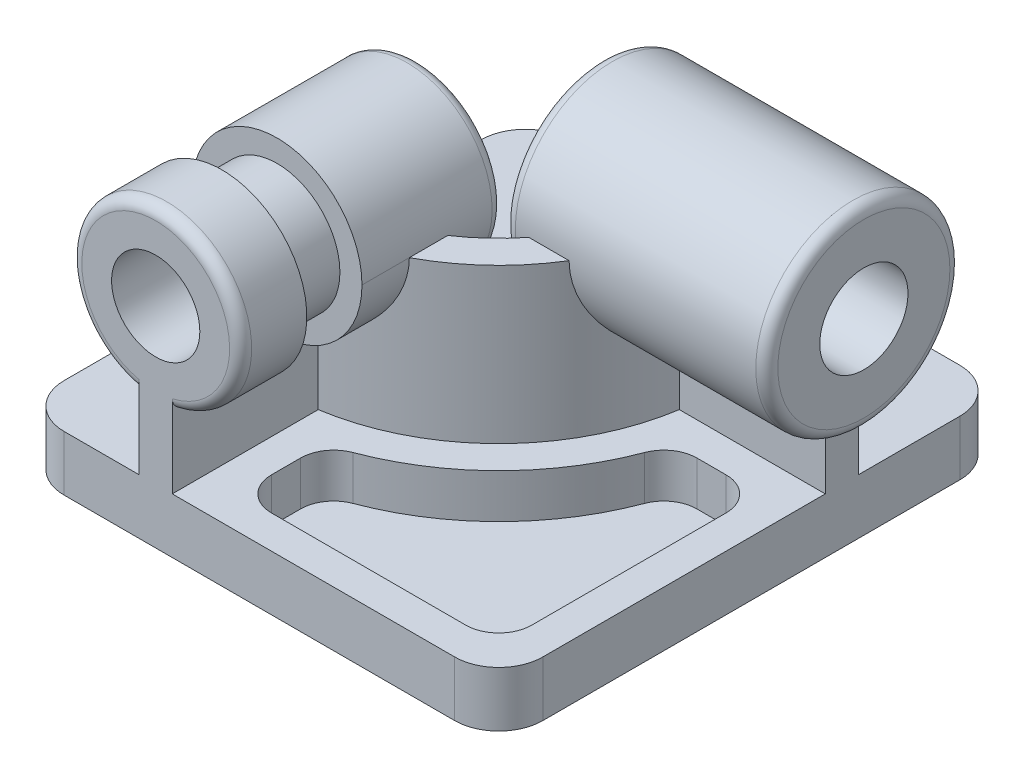
SolidWorks part; units mm, degrees
material "Alloy Steel"
ref_plane "정면" through (0, 0, 0) normal (0, 0, 1) x (1, 0, 0)
ref_plane "윗면" through (0, 0, 0) normal (0, 1, 0) x (1, 0, 0)
ref_plane "우측면" through (0, 0, 0) normal (1, 0, 0) x (0, 0, -1)
sketch "Sketch1" plane through (0, 0, 0) normal (0, 1, 0) x (1, 0, 0)
  line L0 (15, 15) -> (15, 66.1548)
  line L1 (0, 0) -> (143, 0)
  line L2 (0, 0) -> (0, 80)
  line L3 (83, 163) -> (163, 163)
  line L4 (163, 20) -> (163, 163)
  line L5 (96.8452, 148) -> (148, 148)
  line L8 (15, 15) -> (148, 15) construction
  line L9 (148, 15) -> (148, 148) construction
  line L10 (148, 148) -> (163, 148)
  line L11 (15, 15) -> (15, 0)
  line L12 (30, 30) -> (30, 43.171)
  line L13 (119.829, 133) -> (133, 133)
  line L14 (148, 30) -> (148, 118)
  line L15 (45, 15) -> (133, 15)
  line L16 (163, 0) -> (163, 163) construction
  line L17 (143, 0) -> (-34, 0)
  line L18 (163, 20) -> (163, 209)
  line L19 (143, 229) -> (-34, 229)
  line L20 (-54, 20) -> (-54, 209)
  line L21 (0, 0) -> (163, 0) construction
  arc A0 (0, 80) -> (83, 163) centre (0, 163) ccw
  arc A1 (15, 66.1548) -> (96.8452, 148) centre (0, 163) ccw
  arc A2 (39.7266, 57.2134) -> (105.7866, 123.2734) centre (0, 163) ccw
  arc A3 (133, 15) -> (148, 30) centre (133, 30) ccw
  arc A4 (148, 118) -> (133, 133) centre (133, 118) ccw
  arc A5 (119.829, 133) -> (105.7866, 123.2734) centre (119.829, 118) ccw
  arc A6 (39.7266, 57.2134) -> (30, 43.171) centre (45, 43.171) ccw
  arc A7 (30, 30) -> (45, 15) centre (45, 30) ccw
  arc A8 (163, 209) -> (143, 229) centre (143, 209) ccw
  arc A9 (-54, 20) -> (-34, 0) centre (-34, 20) ccw
  arc A10 (-54, 209) -> (-34, 229) centre (-34, 209) cw
  arc A11 (163, 20) -> (143, 0) centre (143, 20) cw
  point P36 (163, 229)
  point P39 (-54, 0)
  point P42 (-54, 229)
  dimension "D3" = 83
  dimension "D8" = 15
  dimension "D11" = 20
  dimension "D12" = 20
  dimension "D2" = 163
  dimension "D5" = 15
  dimension "D6" = 15
  dimension "D7" = 15
  dimension "D9" = 217
  dimension "D10" = 229
  dimension "D4" = 15
extrude "Boss-Extrude1" add sketch "Sketch1" along normal blind 5 contours L12 A7 L15 A3 L14 A4 L13 A5 A2 A6 region at (101.3033, 0, -61.6967)
extrude "Boss-Extrude2" add sketch "Sketch1<3>" along normal blind 25 contours A1 L0 L11 L1 L4 L10 L5 A7 L12 A6 A2 A5 L13 A4 L14 A3 L15 region at (17.093, 0, -40.5774)
sketch "Sketch1<3>" plane through (0, 0, 0) normal (0, 1, 0) x (1, 0, 0) same geometry as "Sketch1"
extrude "Boss-Extrude3" add sketch "Sketch1<4>" along normal blind 95 contours L0 A1 L5 L10 L4 L3 A0 L2 L1 L11 region at (63.0972, 0, -99.9028)
sketch "Sketch1<4>" plane through (0, 0, 0) normal (0, 1, 0) x (1, 0, 0) same geometry as "Sketch1"
extrude "Boss-Extrude4" add sketch "Sketch1<5>" along normal blind 25 contours A10 L20 A9 L17 L2 A0 L3 L18 A8 L19 region at (25.7589, 0, -147.7124)
sketch "Sketch1<5>" plane through (0, 0, 0) normal (0, 1, 0) x (1, 0, 0) same geometry as "Sketch1"
sketch "Sketch2" plane through (163, 0, 0) normal (1, 0, 0) x (0, 0, -1)
  line L0 (148, 95) -> (163, 95) construction
  circle A0 centre (155.5, 95) radius 44
  dimension "D1" = 88
extrude "Boss-Extrude5" add sketch "Sketch2" against normal blind 109 and the other way blind 10
sketch "Sketch4" plane through (0, 0, 0) normal (0, 0, 1) x (1, 0, 0)
  line L0 (0, 95) -> (15, 95) construction
  circle A0 centre (7.5, 95) radius 38.5
  circle A1 centre (7.5, 95) radius 28.5
  line M4 (15, 25) -> (15, 95)
  line M5 (15, 95) -> (0, 95)
  line M6 (0, 95) -> (0, 25)
  dimension "D1" = 10
  dimension "D2" = 77
extrude "Boss-Extrude6" add sketch "Sketch4" against normal blind 119 contours A1 M4 M6 M5 | A1 A0 M4 M6 | A1 M6 M4 M5 | A1 A0 M6 M4 region at (36.4197, 71.2592, 0) region at (7.5, 61.7907, 0) region at (7.5, 80.9146, 0) region at (7.5, 97.795, 0)
extrude "Cut-Extrude1" cut sketch "Sketch4<3>" against normal blind 55
sketch "Sketch4<3>" plane through (0, 0, 0) normal (0, 0, 1) x (1, 0, 0) same geometry as "Sketch4"
extrude "Boss-Extrude7" add sketch "Sketch4<4>" against normal blind 30
sketch "Sketch4<4>" plane through (0, 0, 0) normal (0, 0, 1) x (1, 0, 0) same geometry as "Sketch4"
hole_wizard "Ø0.15 (40) Diameter Hole2" positions "3DSketch1" profile "Sketch5" hole size "Ø0.15" standard "Ansi Metric" end condition up to next
sketch3d "3DSketch1"
  line L0 (7.5, 95, -30) -> (7.5, 95, 0) construction
  point P0 (7.5, 95, 0)
sketch "Sketch5" plane through (7.5, 95, 0) normal (1, 0, 0) x (0, -1, 0)
  line L0 (0, 0) -> (0, 119)
  line L1 (0, 119) -> (20, 119)
  line L2 (20, 119) -> (20, 0)
  line L5 (20, 0) -> (0, 0)
  line L11 (0, -6.35) -> (0, 107.95) construction
  dimension "관통 구멍 지름" = 40
  dimension "관통 구멍 깊이" = 119
hole_wizard "Ø0.15 (40) Diameter Hole1" positions "3DSketch2" profile "Sketch6" hole size "Ø0.15" standard "Ansi Metric" end condition up to next
sketch3d "3DSketch2"
  line L0 (173, 95, -155.5) -> (54, 95, -155.5) construction
  point P0 (173, 95, -155.5)
sketch "Sketch6" plane through (173, 95, -155.5) normal (0, 1, 0) x (0, 0, -1)
  line L0 (0, 0) -> (0, 119)
  line L1 (0, 119) -> (20, 119)
  line L2 (20, 119) -> (20, 0)
  line L5 (20, 0) -> (0, 0)
  line L11 (0, -6.35) -> (0, 107.95) construction
  dimension "관통 구멍 지름" = 40
  dimension "관통 구멍 깊이" = 119
fillet "Fillet1" radius 5 4 edges at (54, 95, -199.5) (173, 95, -199.5) (46, 95, -119) (7.5, 133.5, 0)
